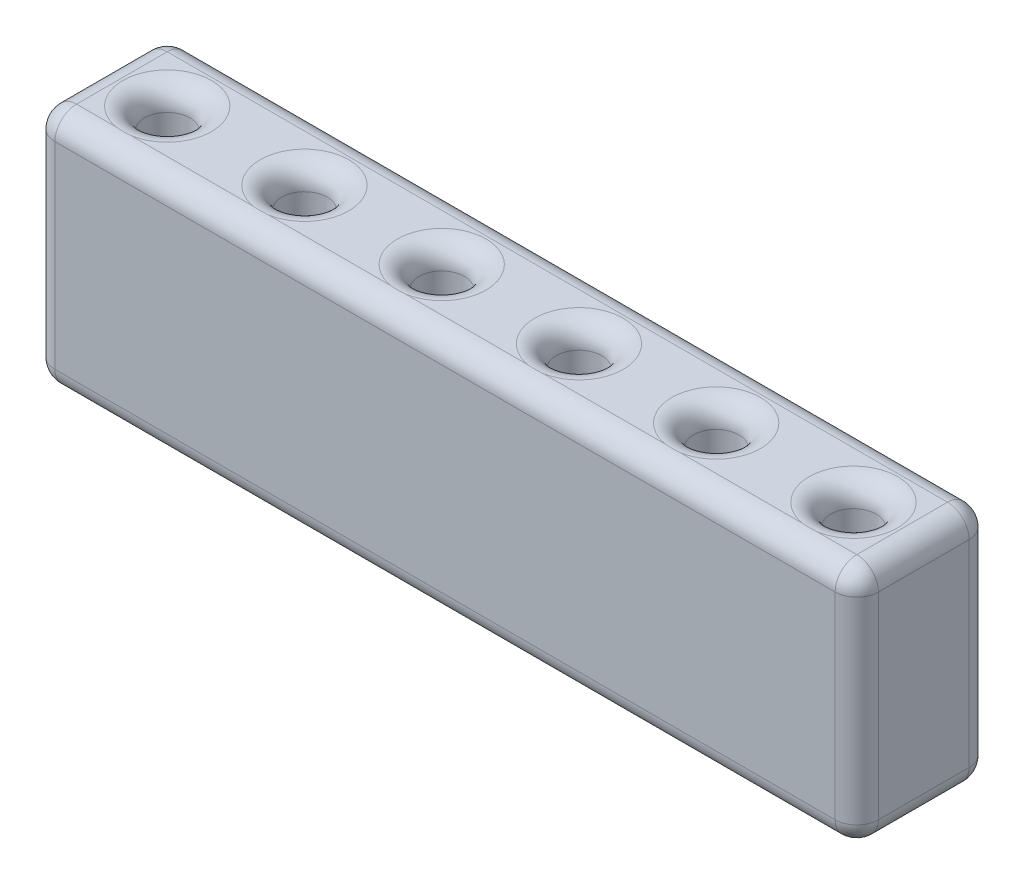
SolidWorks part; units mm, degrees
ref_plane "Front Plane" through (0, 0, 0) normal (0, 0, 1) x (1, 0, 0)
ref_plane "Top Plane" through (0, 0, 0) normal (0, 1, 0) x (1, 0, 0)
ref_plane "Right Plane" through (0, 0, 0) normal (1, 0, 0) x (0, 0, -1)
sketch "Sketch1" plane through (0, 0, 0) normal (0, 0, 1) x (1, 0, 0)
  line L1 (0, 0) -> (-76.2, 0)
  line L2 (0, 0) -> (0, -22.2504)
  line L3 (0, -22.2504) -> (-76.2, -22.2504)
  line L4 (-76.2, 0) -> (-76.2, -22.2504)
  dimension "D1" = 22.2504
  dimension "D2" = 76.2
extrude "Boss-Extrude1" add sketch "Sketch1" along normal blind 12.3952
sketch "Sketch2" plane through (0, 0, 0) normal (0, 1, 0) x (1, 0, 0)
  line L0 (0, 0) -> (-76.2, 0) construction
  line L1 (-76.2, -12.3952) -> (-76.2, 0) construction
  circle A0 centre (-69.85, -6.35) radius 2.1
  circle A4 centre (-57.15, -6.35) radius 2.1
  circle A5 centre (-44.45, -6.35) radius 2.1
  circle A6 centre (-31.75, -6.35) radius 2.1
  circle A7 centre (-19.05, -6.35) radius 2.1
  circle A8 centre (-6.35, -6.35) radius 2.1
  dimension "D1" = 4.2
  dimension "D2" = 6
  dimension "D5" = 6.35
  dimension "D9" = 6.35
extrude "Cut-Extrude1" cut sketch "Sketch2" against normal up to next
fillet "Fillet1" radius 2 24 edges at (-76.2, -22.2504, 6.1976) (-38.1, -22.2504, 12.3952) (0, -22.2504, 6.1976) (-38.1, -22.2504, 0) (-8.45, -22.2504, 6.35) (-21.15, -22.2504, 6.35) (-33.85, -22.2504, 6.35) (-46.55, -22.2504, 6.35) (-59.25, -22.2504, 6.35) (-71.95, -22.2504, 6.35) (0, 0, 6.1976) (-38.1, 0, 12.3952) (-76.2, 0, 6.1976) (-38.1, 0, 0) (-8.45, 0, 6.35) (-21.15, 0, 6.35) (-33.85, 0, 6.35) (-46.55, 0, 6.35) (-59.25, 0, 6.35) (-71.95, 0, 6.35) (0, -11.1252, 12.3952) (-76.2, -11.1252, 12.3952) (-76.2, -11.1252, 0) (0, -11.1252, 0)
